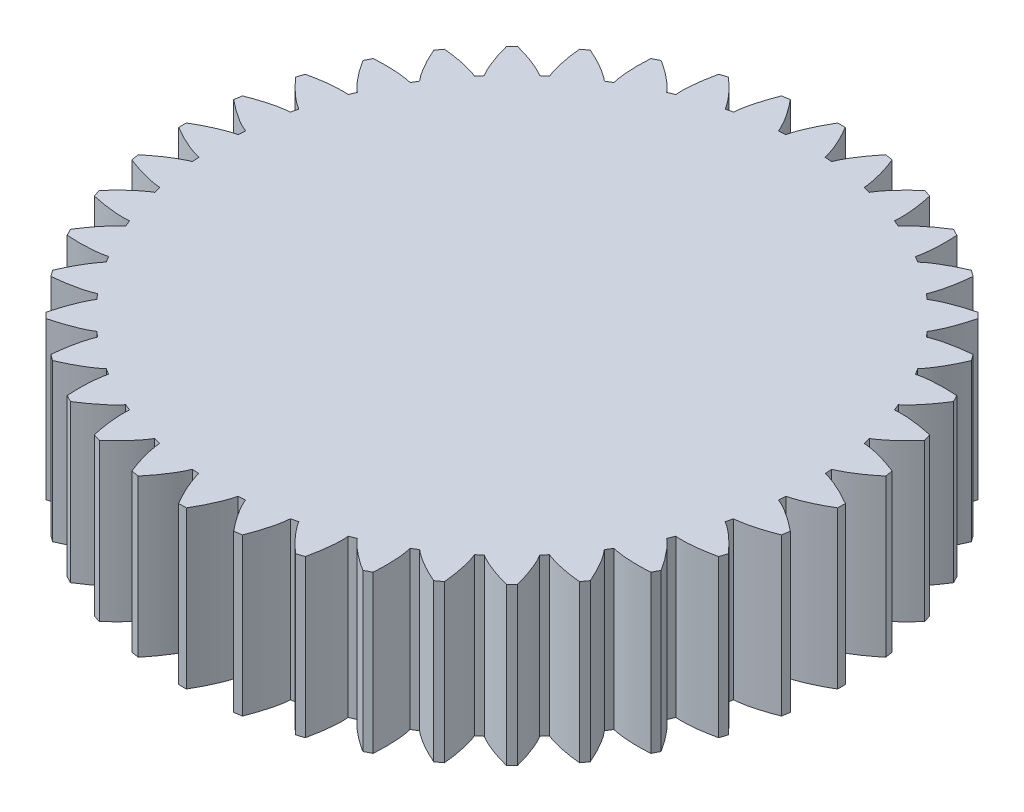
SolidWorks part; units mm, degrees
ref_plane "Front" through (0, 0, 0) normal (0, 0, 1) x (1, 0, 0)
ref_plane "Top" through (0, 0, 0) normal (0, 1, 0) x (1, 0, 0)
ref_plane "Right" through (0, 0, 0) normal (1, 0, 0) x (0, 0, -1)
sketch "Sketch1" plane through (0, 0, 0) normal (0, 1, 0) x (1, 0, 0)
  line L0 (0, 0) -> (0, 33.4864) construction
  line L1 (0, 0) -> (0.7854, 19.9846) construction
  line L16 (0, 0) -> (-0.7854, 19.9846) construction
  line L17 (1.2499, 18.7083) -> (0.4173, 20.9959) construction
  line L18 (-0.4173, 20.9959) -> (-1.2499, 18.7083) construction
  line L19 (0, 0) -> (-3.2885, 20.7409) construction
  line L20 (-2.8757, 20.8022) -> (-1.6951, 18.6732) construction
  line L22 (0, 0) -> (-2.3538, 19.861) construction
  line L29 (1.2499, 18.7083) -> (0.4173, 20.9959) construction
  line L30 (-0.4173, 20.9959) -> (-1.2499, 18.7083) construction
  line L31 (1.2499, 18.7083) -> (0, 0) construction
  line L32 (-1.6951, 18.6732) -> (0, 0) construction
  line L33 (-0.4173, 20.9959) -> (-1.2499, 18.7083) construction
  line L34 (-1.2499, 18.7083) -> (-0.4173, 20.9959) construction
  line L35 (0.4173, 20.9959) -> (1.2499, 18.7083) construction
  line L36 (0.4173, 20.9959) -> (1.2499, 18.7083) construction
  line L37 (-1.6951, 18.6732) -> (0, 0)
  line L38 (1.2499, 18.7083) -> (0, 0)
  circle A0 centre (0, 0) radius 18.75 construction
  circle A1 centre (0, 0) radius 20 construction
  circle A2 centre (0, 0) radius 21 construction
  arc A5 (-1.6951, 18.6732) -> (-1.2499, 18.7083) centre (0, 0) cw
  arc A7 (-0.4173, 20.9959) -> (0.4173, 20.9959) centre (0, 0) cw construction
  arc A10 (-0.4173, 20.9959) -> (0.4173, 20.9959) centre (0, 0) cw construction
  arc A12 (-0.2451, 20.9986) -> (0.2451, 20.9986) centre (0, 0) cw
  spline S0 degree 4 poles (1.2499, 18.7083) (1.2493, 18.7119) (1.2473, 18.7222) (1.2434, 18.7415) (1.2364, 18.7729) (1.2267, 18.8128) (1.2134, 18.8643) (1.1967, 18.9248) (1.1772, 18.9912) (1.1547, 19.0632) (1.1311, 19.135) (1.1067, 19.2066) (1.0813, 19.2777) (1.0496, 19.3638) (1.01, 19.4669) (0.9615, 19.5873) (0.9039, 19.7236) (0.8423, 19.8623) (0.7794, 19.9986) (0.7131, 20.1362) (0.6471, 20.2693) (0.5757, 20.4073) (0.5084, 20.5347) (0.4299, 20.6773) (0.3656, 20.7924) (0.2775, 20.9441) (0.2245, 21.0337) (0.1613, 21.1385) (0.1326, 21.185) (0.1149, 21.2137) knots 0 0 0 0 0 0.005377 0.015084 0.028532 0.04661 0.064855 0.092111 0.119476 0.146842 0.174209 0.201575 0.228941 0.256307 0.307035 0.361767 0.4165 0.471232 0.525964 0.580697 0.635429 0.690161 0.744894 0.799626 0.854358 0.909091 0.954545 1 1 1 1 1 construction
  spline S1 degree 4 poles (1.2499, 18.7083) (1.2493, 18.7119) (1.2473, 18.7222) (1.2434, 18.7415) (1.2364, 18.7729) (1.2267, 18.8128) (1.2134, 18.8643) (1.1967, 18.9248) (1.1772, 18.9912) (1.1547, 19.0632) (1.1311, 19.135) (1.1067, 19.2066) (1.0813, 19.2777) (1.0496, 19.3638) (1.01, 19.4669) (0.9615, 19.5873) (0.9039, 19.7236) (0.8423, 19.8623) (0.7794, 19.9986) (0.7131, 20.1362) (0.6471, 20.2693) (0.5757, 20.4073) (0.5084, 20.5347) (0.4299, 20.6773) (0.3656, 20.7924) (0.2966, 20.9112) (0.2627, 20.969) (0.2451, 20.9986) knots 0 0 0 0 0 0.005377 0.015084 0.028532 0.04661 0.064855 0.092111 0.119476 0.146842 0.174209 0.201575 0.228941 0.256307 0.307035 0.361767 0.4165 0.471232 0.525964 0.580697 0.635429 0.690161 0.744894 0.799626 0.854358 0.909092 0.909092 0.909092 0.909092 0.909092
  spline S2 degree 4 poles (-1.2499, 18.7083) (-1.2493, 18.7119) (-1.2473, 18.7222) (-1.2434, 18.7415) (-1.2364, 18.7729) (-1.2267, 18.8128) (-1.2134, 18.8643) (-1.1967, 18.9248) (-1.1772, 18.9912) (-1.1547, 19.0632) (-1.1311, 19.135) (-1.1067, 19.2066) (-1.0813, 19.2777) (-1.0496, 19.3638) (-1.01, 19.4669) (-0.9615, 19.5873) (-0.9039, 19.7236) (-0.8423, 19.8623) (-0.7794, 19.9986) (-0.7131, 20.1362) (-0.6471, 20.2693) (-0.5757, 20.4073) (-0.5084, 20.5347) (-0.4299, 20.6773) (-0.3656, 20.7924) (-0.2775, 20.9441) (-0.2245, 21.0337) (-0.1613, 21.1385) (-0.1326, 21.185) (-0.1149, 21.2137) knots 0 0 0 0 0 0.005377 0.015084 0.028532 0.04661 0.064855 0.092111 0.119476 0.146842 0.174209 0.201575 0.228941 0.256307 0.307035 0.361767 0.4165 0.471232 0.525964 0.580697 0.635429 0.690161 0.744894 0.799626 0.854358 0.909091 0.954545 1 1 1 1 1 construction
  spline S3 degree 4 poles (-1.2499, 18.7083) (-1.2493, 18.7119) (-1.2473, 18.7222) (-1.2434, 18.7415) (-1.2364, 18.7729) (-1.2267, 18.8128) (-1.2134, 18.8643) (-1.1967, 18.9248) (-1.1772, 18.9912) (-1.1547, 19.0632) (-1.1311, 19.135) (-1.1067, 19.2066) (-1.0813, 19.2777) (-1.0496, 19.3638) (-1.01, 19.4669) (-0.9615, 19.5873) (-0.9039, 19.7236) (-0.8423, 19.8623) (-0.7794, 19.9986) (-0.7131, 20.1362) (-0.6471, 20.2693) (-0.5757, 20.4073) (-0.5084, 20.5347) (-0.4299, 20.6773) (-0.3656, 20.7924) (-0.2966, 20.9112) (-0.2627, 20.969) (-0.2451, 20.9986) knots 0 0 0 0 0 0.005377 0.015084 0.028532 0.04661 0.064855 0.092111 0.119476 0.146842 0.174209 0.201575 0.228941 0.256307 0.307035 0.361767 0.4165 0.471232 0.525964 0.580697 0.635429 0.690161 0.744894 0.799626 0.854358 0.909092 0.909092 0.909092 0.909092 0.909092
  point P19 (1.1224, 31.659)
  point P26 (0, 0)
  point P27 (0, 0)
  point P28 (0, 0)
  point P29 (0, 0)
  point P30 (0, 0)
  point P31 (-1.2499, 18.6732)
  point P32 (0.9997, 20.9959)
  dimension "D1" = 40
  dimension "D2" = 37.5
  dimension "D3" = 42
  dimension "D4" = 40
  dimension "D5" = 1.5708
  dimension "D8" = 3.1416
  dimension "D6" = 0.7854
  dimension "D7" = 20
extrude "Boss-Extrude1" add sketch "Sketch1" along normal blind 10
pattern_circular "CirPattern1" count 40 over 360 about axis through (0, 10, 0) along (0, -1, 0) of "Boss-Extrude1"
equation "\"Reference_Diameter\" = 40"
equation "\"Reference_Radius\"= \"Reference_Diameter\" / 2"
equation "\"Module\"= \"Reference_Diameter\" / \"Teeth\""
equation "\"Teeth\"= 40'The Number of Teeth"
equation "\"Pitch\"= \"Module\" * PI"
equation "\"Tooth_Depth\"= \"Module\" * 2.25"
equation "\"Addendum\"= \"Module\"'Distance above reference"
equation "\"Dedendum\"= \"Module\" * 1.25'Distance below reference"
equation "\"Tooth_Thickness\"= ( \"Module\" * PI ) / 2"
equation "\"Tip_Diameter\"= \"Reference_Diameter\" + ( 2 * \"Module\" )"
equation "\"Root_Diameter\"= \"Reference_Diameter\" - ( 2.5 * \"Module\" )"
equation "\"Pressure_Angle\"= 20deg"
equation "\"D2@Sketch1\" = \"Root_Diameter\""
equation "\"D1@Sketch1\"= \"Reference_Diameter\""
equation "\"D3@Sketch1\"= \"Tip_Diameter\""
equation "\"D5@Sketch1\"= \"Tooth_Thickness\""
equation "\"D4@Sketch1\"= \"Pressure_Angle\" * 2"
equation "\"D8@Sketch1\"= \"Pitch\""
equation "\"D6@Sketch1\"= \"Tooth_Thickness\" / 2"
equation "\"D7@Sketch1\"= \"Pressure_Angle\""
